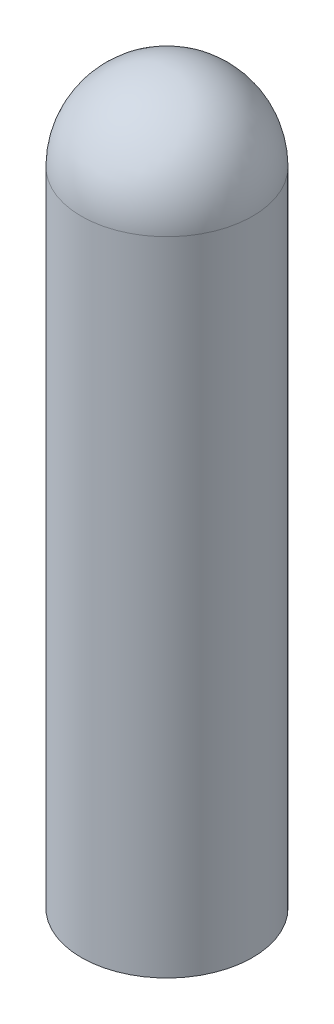
SolidWorks part; units mm, degrees
ref_plane "Front Plane" through (0, 0, 0) normal (0, 0, 1) x (1, 0, 0)
ref_plane "Top Plane" through (0, 0, 0) normal (0, 1, 0) x (1, 0, 0)
ref_plane "Right Plane" through (0, 0, 0) normal (1, 0, 0) x (0, 0, -1)
sketch "Sketch1" plane through (0, 0, 0) normal (0, 1, 0) x (1, 0, 0)
  circle A0 centre (0, 0) radius 2
  dimension "D1" = 4
extrude "Boss-Extrude1" add sketch "Sketch1" along normal blind 15 contours A0
sketch "Sketch2" plane through (0, 0, 0) normal (0, 0, 1) x (1, 0, 0)
  line L0 (2, 15) -> (-2, 15) construction
  line L2 (2, 15) -> (-2, 15)
  arc A2 (2, 15) -> (-2, 15) centre (0, 15) ccw
revolve "Revolve1" add sketch "Sketch2" angle 360 about L2
